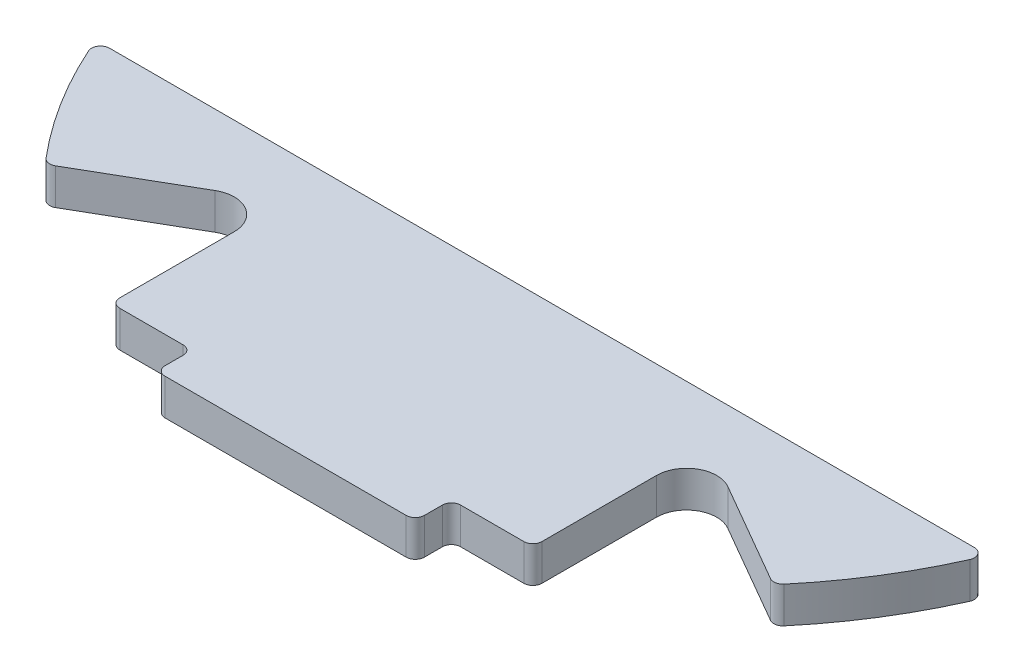
SolidWorks part; units mm, degrees
material "Acier non allié"
ref_plane "Front" through (0, 0, 0) normal (0, 0, 1) x (1, 0, 0)
ref_plane "Top" through (0, 0, 0) normal (0, 1, 0) x (1, 0, 0)
ref_plane "Right" through (0, 0, 0) normal (1, 0, 0) x (0, 0, -1)
sketch "Esquisse1" plane through (0, 0, 0) normal (0, 1, 0) x (1, 0, 0)
  line L2 (0, 0) -> (0, 85)
  line L4 (70, 12) -> (70, 70.2872)
  line L5 (0, 85) -> (147.9155, 85)
  line L7 (120.727, 41) -> (70, 70.2872)
  line L8 (70, 12) -> (43, 12)
  line L9 (43, 12) -> (43, 0)
  line L10 (43, 0) -> (0, 0)
  arc A0 (120.727, 41) -> (147.9155, 85) centre (0, 146) ccw
  dimension "D4" = 61
  dimension "D7" = 160
  dimension "D1" = 60
  dimension "D2" = 12
  dimension "D3" = 73
  dimension "D5" = 70
  dimension "D6" = 43
  dimension "D8" = 147.9155
  dimension "D9" = 44
base flange "Tôle de base pliée1" sketch "Esquisse1" thickness 12 reverse thickness direction yes parameters "D1"=1
fillet "Congé1" radius 10 1 edges at (70, 6, -70.2872)
fillet "Congé2" radius 3 5 edges at (70, 6, -12) (43, 6, -12) (43, 6, 0) (147.9155, 6, -85) (120.727, 6, -41)
mirror "Symétrie1" about plane through (0, 12, 0) normal (1, 0, 0) of bodies 101
sketch "Lignes de pliage1" [suppressed] plane through (0, 0, 0) normal (0, 1, 0) x (1, 0, 0)
sketch "Cube de visualisation1" [suppressed] plane through (0, 0, 0) normal (0, 1, 0) x (1, 0, 0)
sheet metal parameters "Tôlerie1" thickness 12 parameters "D1"=1
flat pattern "Etat déplié1" [suppressed]
sketch "Lignes de pliage2" plane through (0, 0, 0) normal (0, 1, 0) x (1, 0, 0)
sketch3d "Cube de visualisation2" [suppressed]
  line L0 (0, 88, 0) -> (-150, 88, 0) construction
  line L1 (0, 0, 0) -> (-150, 0, 0) construction
  line L2 (0, 88, 0) -> (0, 0, 0) construction
  line L3 (-150, 88, 0) -> (-150, 0, 0) construction
sheet metal parameters "Tôlerie2" thickness 12 parameters "D1"=1
flat pattern "Etat déplié2"
sketch "Lignes de pliage3" plane through (0, 0, 0) normal (0, 1, 0) x (1, 0, 0)
sketch3d "Cube de visualisation3" [suppressed]
  line L0 (-146.3632, -146, 0) -> (146.3632, -146, 0) construction
  line L1 (-146.3632, -61, 0) -> (146.3632, -61, 0) construction
  line L2 (-146.3632, -146, 0) -> (-146.3632, -61, 0) construction
  line L3 (146.3632, -146, 0) -> (146.3632, -61, 0) construction
